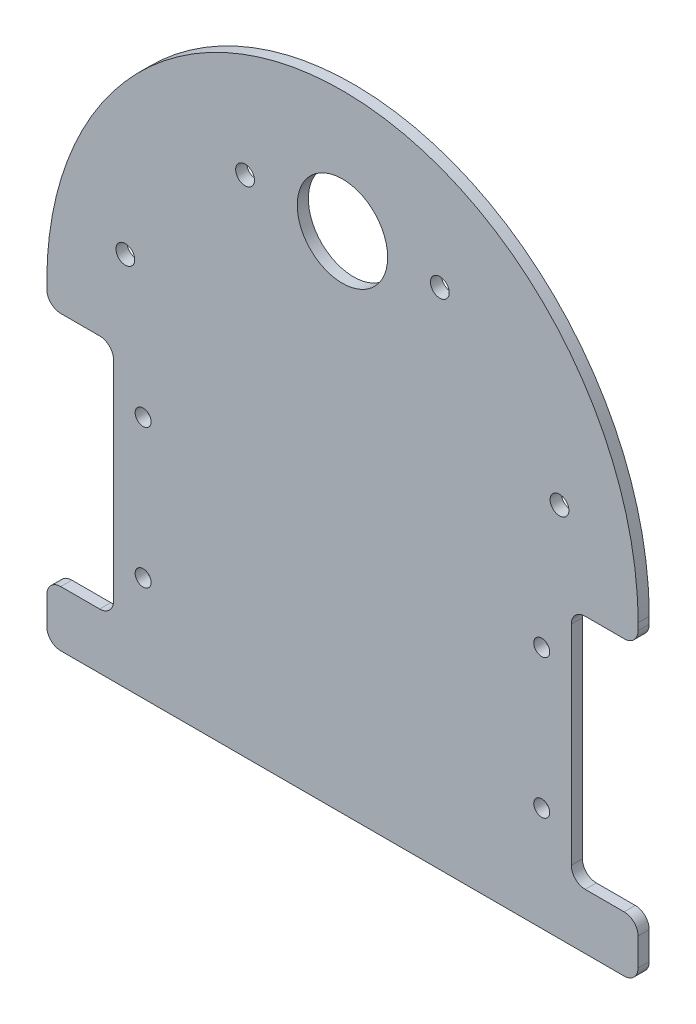
SolidWorks part; units mm, degrees
material "A-Glass Fiber"
ref_plane "Top Plane" through (0, 0, 0) normal (0, 0, 1) x (1, 0, 0)
ref_plane "Right Plane" through (0, 0, 0) normal (0, 1, 0) x (1, 0, 0)
ref_plane "Front Plane" through (0, 0, 0) normal (1, 0, 0) x (0, 0, -1)
sketch "Sketch1" plane through (0, 0, 0) normal (0, 0, 1) x (1, 0, 0)
  line L1 (42.5, -45) -> (-42.5, -45)
  line L2 (42.5, -45) -> (42.5, 45)
  line L3 (42.5, 45) -> (-42.5, 45)
  line L4 (-42.5, -45) -> (-42.5, 45)
  line L5 (42.5, -45) -> (-42.5, 45) construction
  line L6 (42.5, 45) -> (-42.5, -45) construction
  point P0 (0, 0)
  dimension "D1" = 85
  dimension "D2" = 90
extrude "Boss-Extrude1" add sketch "Sketch1" along normal blind 1.6
sketch "Sketch2" plane through (0, 0, 1.6) normal (0, 0, 1) x (1, 0, 0)
  line L0 (-42.5, 45) -> (-42.5, -45) construction
  line L1 (42.5, 45) -> (-42.5, 45) construction
  line L6 (-42.5, 0) -> (-70, 0)
  line L7 (-70, 0) -> (-70, 70)
  line L8 (42.5, -45) -> (42.5, 45) construction
  line L9 (-70, 70) -> (70, 70)
  line L10 (70, 70) -> (70, 0)
  line L11 (70, 0) -> (42.5, 0)
  ellipse E0 centre (0, 0) end of major axis (0, -45) minor radius 42.5 (42.5, 0) -> (-42.5, 0) ccw
  point P14 (0, 70)
  dimension "D1" = 140
  dimension "D2" = 70
extrude "Cut-Extrude1" cut sketch "Sketch2" against normal through all
sketch "Sketch3" plane through (0, 0, 1.6) normal (0, 0, 1) x (1, 0, 0)
  line L1 (-42.5, -3) -> (-32.9, -3)
  line L2 (-42.5, -3) -> (-42.5, -37)
  line L3 (-42.5, -37) -> (-32.9, -37)
  line L4 (-32.9, -3) -> (-32.9, -37)
  line L6 (0, -0.88) -> (0, 0.88) construction
  line L7 (42.5, -3) -> (32.9, -3)
  line L8 (42.5, -37) -> (32.9, -37)
  line L9 (32.9, -3) -> (32.9, -37)
  line L10 (42.5, -3) -> (42.5, -37)
  line L11 (-42.5, 0) -> (-42.5, -45) construction
  line L13 (-42.5, -45) -> (42.5, -45) construction
  dimension "D1" = 9.6
  dimension "D2" = 34
  dimension "D3" = 8
extrude "Cut-Extrude2" cut sketch "Sketch3" against normal through all
sketch "Sketch4" plane through (0, 0, 1.6) normal (0, 0, 1) x (1, 0, 0)
  line L0 (-42.5, -45) -> (42.5, -45) construction
  circle A0 centre (0, 27.5) radius 6.5
  dimension "D1" = 13
  dimension "D2" = 72.5
extrude "Cut-Extrude3" cut sketch "Sketch4" against normal through all
sketch "Sketch5" plane through (0, 0, 1.6) normal (0, 0, 1) x (1, 0, 0)
  line L1 (-32.9, -37) -> (-32.9, -3) construction
  line L2 (-28.65, -10) -> (-28.65, -30) construction
  line L3 (0, -0.88) -> (0, 0.88) construction
  line L4 (-1016.15, -20) -> (48983.85, -20) construction
  line L5 (0, -1000) -> (0, 49000) construction
  circle A0 centre (-28.65, -10) radius 1.15
  circle A1 centre (-28.65, -30) radius 1.15
  circle A2 centre (28.65, -30) radius 1.15
  circle A3 centre (28.65, -10) radius 1.15
  point P2 (-28.65, -20)
  point P14 (-32.9, -20)
  dimension "D3" = 2.3
  dimension "D1" = 4.25
  dimension "D2" = 20
extrude "Cut-Extrude4" cut sketch "Sketch5" against normal through all
sketch "Sketch6" plane through (0, 0, 1.6) normal (0, 0, 1) x (1, 0, 0)
  line L0 (-14, 27.5) -> (14, 27.5) construction
  circle A1 centre (-14, 27.5) radius 1.35
  circle A2 centre (14, 27.5) radius 1.35
  point P5 (0, 27.5)
  dimension "D2" = 2.7
  dimension "D1" = 28
extrude "Cut-Extrude5" cut sketch "Sketch6" against normal through all
fillet "Fillet1" radius 2 10 edges at (42.5, -37, 0.8) (32.9, -37, 0.8) (32.9, -3, 0.8) (42.5, -3, 0.8) (-32.9, -37, 0.8) (-32.9, -3, 0.8) (-42.5, -37, 0.8) (-42.5, -3, 0.8) (42.5, -45, 0.8) (-42.5, -45, 0.8)
sketch "Sketch7" plane through (0, 0, 1.6) normal (0, 0, 1) x (1, 0, 0)
  line L0 (-40.5, -45) -> (40.5, -45) construction
  line L1 (0, -63.3642) -> (0, 76.6358) construction
  line L2 (-31.2085, 9) -> (31.2085, 9) construction
  circle A0 centre (-31.2085, 9) radius 1.35
  circle A1 centre (31.2085, 9) radius 1.35
  point P4 (0, 9)
  dimension "D1" = 2.7
  dimension "D2" = 54
  dimension "D3" = 62.417
extrude "Cut-Extrude6" cut sketch "Sketch7" against normal blind 10
equation "\"Motor_Position\"= 8"
equation "\"D3@Sketch3\"=\"Motor_Position\""
equation "\"Caster_Position\"= 72.5"
equation "\"D2@Sketch4\"=\"Caster_Position\""
equation "\"Battery_position\"= 54mm"
equation "\"D2@Sketch7\"=\"Battery_position\""
